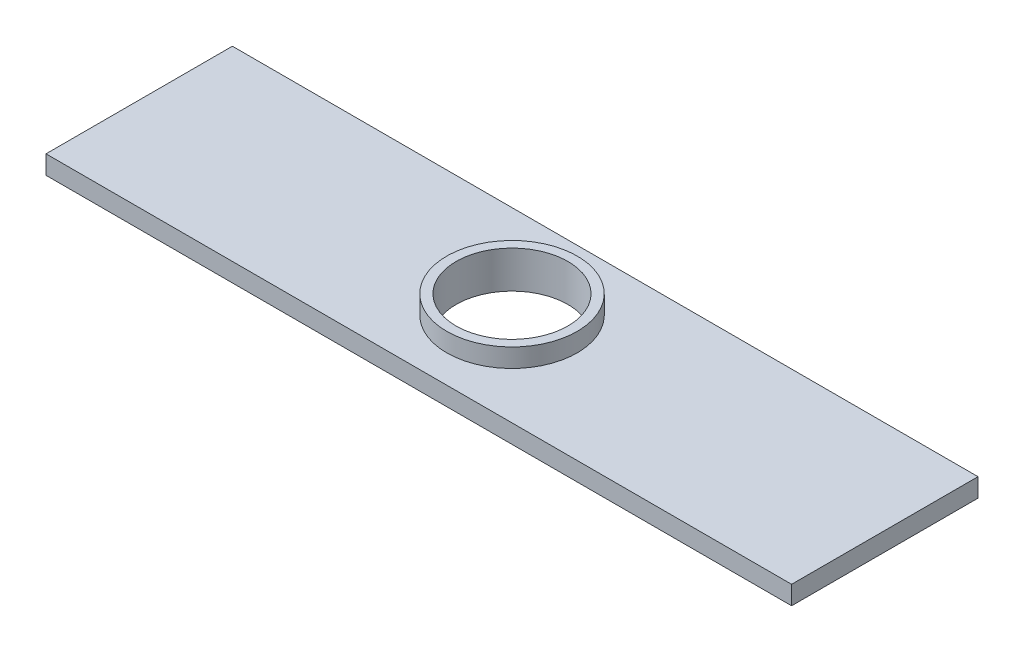
SolidWorks part; units mm, degrees
ref_plane "Front Plane" through (0, 0, 0) normal (0, 0, 1) x (1, 0, 0)
ref_plane "Top Plane" through (0, 0, 0) normal (0, 1, 0) x (1, 0, 0)
ref_plane "Right Plane" through (0, 0, 0) normal (1, 0, 0) x (0, 0, -1)
sketch "Sketch1" plane through (0, 0, 0) normal (0, 1, 0) x (1, 0, 0)
  line L1 (-100, -25) -> (100, -25)
  line L2 (-100, -25) -> (-100, 25)
  line L3 (-100, 25) -> (100, 25)
  line L4 (100, -25) -> (100, 25)
  line L5 (-100, -25) -> (100, 25) construction
  line L6 (-100, 25) -> (100, -25) construction
  circle A0 centre (0, 0) radius 15
  circle A1 centre (0, 0) radius 17.5
  dimension "D1" = 30
  dimension "D2" = 35
  dimension "D3" = 50
  dimension "D4" = 200
extrude "Boss-Extrude1" add sketch "Sketch1" along normal blind 5 contours A1 A0 region at (-17.005, 0, 0)
extrude "Boss-Extrude2" add sketch "Sketch1<3>" against normal blind 5 contours L1 L4 L3 L2 A1 | A1 A0 region at (-97.9384, 0, 0) region at (-17.005, 0, 0)
sketch "Sketch1<3>" plane through (0, 0, 0) normal (0, 1, 0) x (1, 0, 0) same geometry as "Sketch1"
